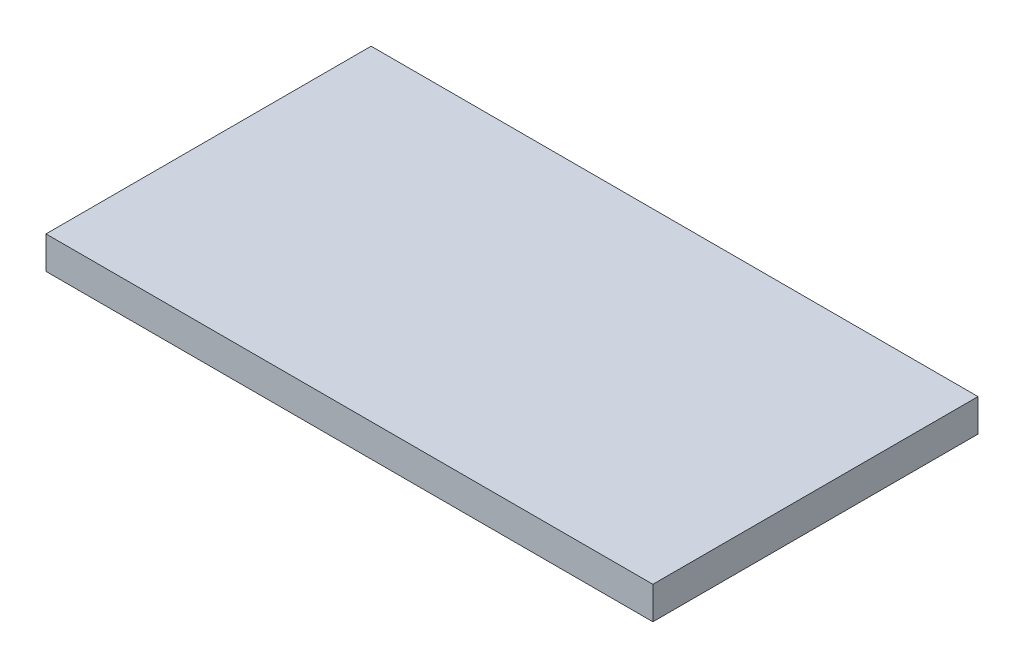
SolidWorks part; units mm, degrees
material "Maple"
ref_plane "Front Plane" through (0, 0, 0) normal (0, 0, 1) x (1, 0, 0)
ref_plane "Top Plane" through (0, 0, 0) normal (0, 1, 0) x (1, 0, 0)
ref_plane "Right Plane" through (0, 0, 0) normal (1, 0, 0) x (0, 0, -1)
sketch "Sketch1" plane through (0, 0, 0) normal (0, 1, 0) x (1, 0, 0)
  line L1 (0, 0) -> (1422.4, 0)
  line L2 (0, 0) -> (0, 762)
  line L3 (0, 762) -> (1422.4, 762)
  line L4 (1422.4, 0) -> (1422.4, 762)
  dimension "D1" = 762
  dimension "D2" = 1422.4
extrude "Boss-Extrude1" add sketch "Sketch1" along normal blind 76.2
